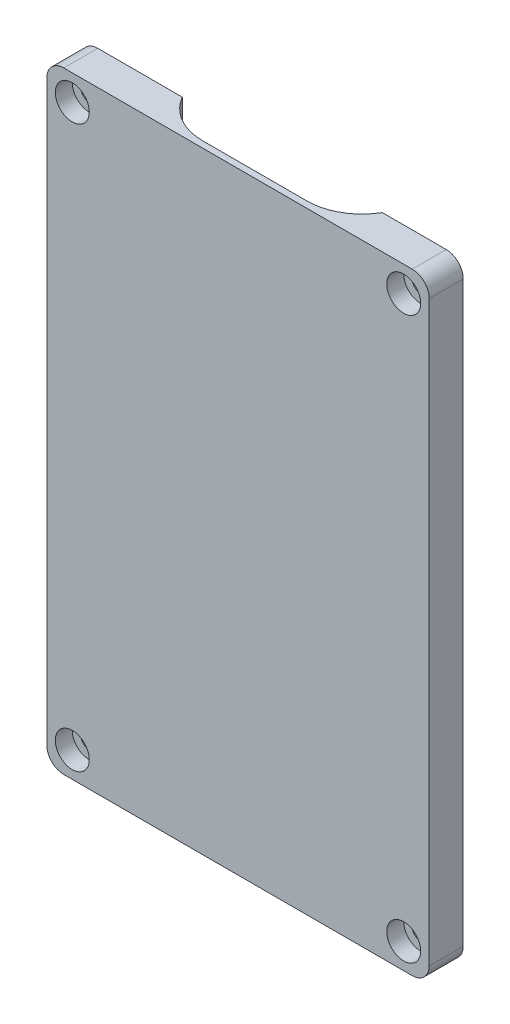
SolidWorks part; units mm, degrees
other "标注1"
sketch "草图6" plane through (-121.7901, 77.7286, -9) normal (-0.0529, 0.1135, -0.9921) x (-0.9984, 0.0112, 0.0545)
ref_plane "前视基准面" through (0, 0, 0) normal (0, 0, 1) x (1, 0, 0)
ref_plane "上视基准面" through (0, 0, 0) normal (0, 1, 0) x (1, 0, 0)
ref_plane "右视基准面" through (0, 0, 0) normal (1, 0, 0) x (0, 0, -1)
sketch "草图1" plane through (0, 0, 0) normal (0, 0, 1) x (1, 0, 0)
  line L1 (-97.7901, 77.7286) -> (-120.2901, 77.7286)
  line L2 (-97.7901, 77.7286) -> (-97.7901, 41.7286)
  line L3 (-97.7901, 41.7286) -> (-120.2901, 41.7286)
  line L4 (-120.2901, 77.7286) -> (-120.2901, 41.7286)
  dimension "D1" = 22.5
  dimension "D2" = 36
extrude "凸台-拉伸1" add sketch "草图1" along normal blind 2
sketch "草图9" plane through (0, 0, 2) normal (0, 0, 1) x (1, 0, 0)
  line L1 (-97.7901, 41.7286) -> (-97.7901, 77.7286) construction
  line L5 (-120.2901, 41.7286) -> (-97.7901, 41.7286) construction
  line L6 (-120.2901, 77.7286) -> (-120.2901, 41.7286) construction
  line L7 (-97.7901, 77.7286) -> (-120.2901, 77.7286) construction
  circle A0 centre (-99.2901, 76.2286) radius 1
  circle A1 centre (-99.2901, 43.2286) radius 1
  circle A2 centre (-118.7901, 43.2286) radius 1
  circle A3 centre (-118.7901, 76.2286) radius 1
  dimension "D1" = 1.5
  dimension "D2" = 1.5
  dimension "D4" = 1.5
  dimension "D5" = 1.5
extrude "切除-拉伸3" cut sketch "草图9" against normal blind 1
sketch "草图10" plane through (0, 0, 1) normal (0, 0, 1) x (1, 0, 0)
  circle A0 centre (-118.7901, 43.2286) radius 0.5
  circle A1 centre (-99.2901, 43.2286) radius 0.5
  circle A2 centre (-99.2901, 76.2286) radius 0.5
  circle A3 centre (-118.7901, 76.2286) radius 0.5
  circle A5 centre (-118.7901, 76.2286) radius 1 construction
  circle A6 centre (-99.2901, 76.2286) radius 1 construction
  circle A7 centre (-118.7901, 43.2286) radius 1 construction
  circle A8 centre (-99.2901, 43.2286) radius 1 construction
  dimension "D1" = 1
extrude "切除-拉伸4" cut sketch "草图10" against normal up to next
fillet "圆角1" radius 1 4 edges at (-97.7901, 77.7286, 1) (-97.7901, 41.7286, 1) (-120.2901, 41.7286, 1) (-120.2901, 77.7286, 1)
sketch "草图11" plane through (0, 0, 0) normal (0, 0, -1) x (-1, 0, 0)
  line L0 (98.7901, 77.7286) -> (119.2901, 77.7286) construction
  line L1 (105.3271, 67.5286) -> (111.0901, 67.5286)
  line L2 (105.3271, 67.5286) -> (105.3271, 64.8729)
  line L3 (105.3271, 64.8729) -> (111.0901, 64.8729)
  line L4 (111.0901, 67.5286) -> (111.0901, 64.8729)
  line L5 (97.7901, 42.7286) -> (97.7901, 76.7286) construction
  dimension "D1" = 10.2
  dimension "D2" = 13.3
extrude "凸台-拉伸2" add sketch "草图11" along normal blind 2.7
sketch "草图12" plane through (0, 0, 0) normal (0, 0, -1) x (-1, 0, 0)
  line L1 (105.0814, 53.2248) -> (113.0814, 53.2248)
  line L2 (105.0814, 53.2248) -> (105.0814, 51.7286)
  line L3 (105.0814, 51.7286) -> (113.0814, 51.7286)
  line L4 (113.0814, 53.2248) -> (113.0814, 51.7286)
  line L5 (98.7901, 77.7286) -> (119.2901, 77.7286) construction
  dimension "D1" = 26
  dimension "D2" = 8
extrude "凸台-拉伸3" add sketch "草图12" along normal blind 2.2
sketch "草图14" plane through (-120.2901, 0, 0) normal (-1, 0, 0) x (0, 0, 1)
  line L1 (0, 75.222) -> (2, 75.222)
  line L2 (0, 75.222) -> (0, 61.7399)
  line L3 (0, 61.7399) -> (2, 61.7399)
  line L4 (2, 75.222) -> (2, 61.7399)
  line L6 (2, 76.7286) -> (2, 42.7286) construction
extrude "切除-拉伸6" cut sketch "草图14" against normal blind 0.0001
fillet "圆角3" radius 2 1 edges at (-120.29, 68.481, 0)
sketch "草图16" plane through (0, 77.7286, 0) normal (0, 1, 0) x (1, 0, 0)
  line L0 (-111.5023, 1.625) -> (-105.3664, 1.625) construction
  line L2 (-111.5023, 4.875) -> (-105.3664, 4.875)
  line L3 (-111.5023, -1.625) -> (-105.3664, -1.625)
  line L4 (-105.3233, 4.875) -> (-111.5233, 4.875) construction
  arc A0 (-111.5023, 4.875) -> (-111.5023, -1.625) centre (-111.5023, 1.625) ccw
  arc A1 (-105.3664, -1.625) -> (-105.3664, 4.875) centre (-105.3664, 1.625) ccw
  arc A4 (-102.5087, 0) -> (-105.3233, 4.875) centre (-105.3233, 1.625) ccw construction
  arc A5 (-111.5233, 4.875) -> (-114.3378, 0) centre (-111.5233, 1.625) ccw construction
  point P4 (-108.4344, 1.625)
extrude "切除-拉伸7" cut sketch "草图16" against normal blind 2.62
fillet "圆角7" radius 1 2 edges at (-120.2901, 61.7399, 1) (-120.2901, 75.222, 1)
